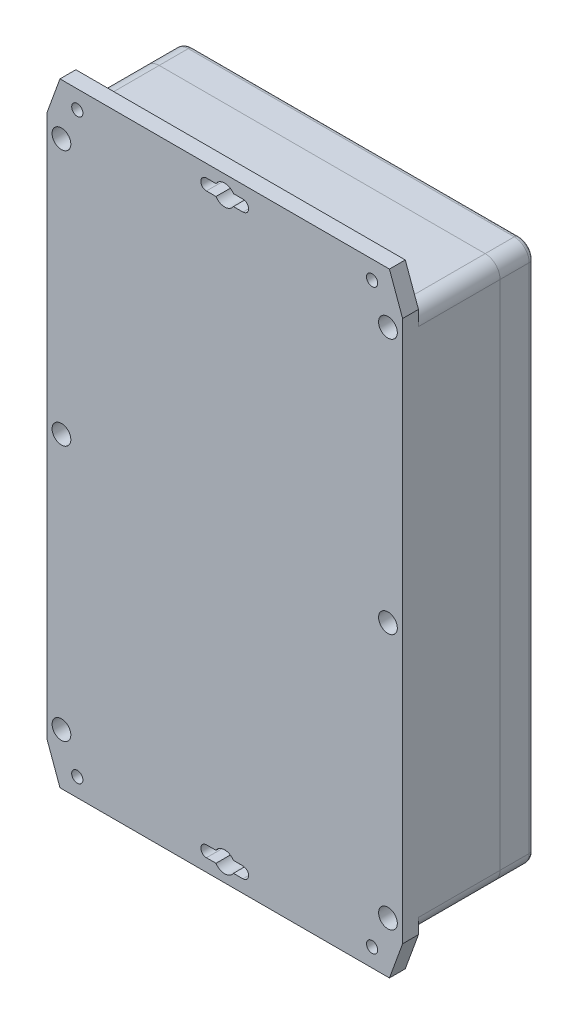
SolidWorks part; units mm, degrees
ref_plane "Front Plane" through (0, 0, 0) normal (0, 0, 1) x (1, 0, 0)
ref_plane "Top Plane" through (0, 0, 0) normal (0, 1, 0) x (1, 0, 0)
ref_plane "Right Plane" through (0, 0, 0) normal (1, 0, 0) x (0, 0, -1)
sketch "Sketch1" plane through (0, 0, 0) normal (0, 0, 1) x (1, 0, 0)
  line L0 (-73.025, -125.9967) -> (73.025, 125.9967) construction
  line L1 (-73.025, 125.9967) -> (73.025, 125.9967)
  line L2 (-73.025, 125.9967) -> (-73.025, -125.9967)
  line L3 (-73.025, -125.9967) -> (73.025, -125.9967)
  line L4 (73.025, 125.9967) -> (73.025, -125.9967)
  line L5 (0, 118.5037) -> (0, -118.5037) construction
  line L6 (-7.5057, 118.5037) -> (7.5057, 118.5037) construction
  line L7 (-7.5057, 120.8024) -> (-3.58, 120.8024)
  line L8 (-7.5057, 116.205) -> (-3.58, 116.205)
  line L9 (3.58, 120.8024) -> (7.5057, 120.8024)
  line L10 (3.58, 116.205) -> (7.5057, 116.205)
  line L11 (-73.025, 0) -> (73.025, 0) construction
  line L12 (-7.5057, -116.205) -> (-3.58, -116.205)
  line L13 (3.58, -116.205) -> (7.5057, -116.205)
  line L14 (3.58, -120.8024) -> (7.5057, -120.8024)
  line L15 (-7.5057, -120.8024) -> (-3.58, -120.8024)
  line L16 (-67.0052, 105.0036) -> (67.0052, -105.0036) construction
  line L17 (0, -114.2492) -> (0, -122.7582) construction
  line L18 (0, 114.2492) -> (0, 122.7582) construction
  line L19 (-60.5028, 118.5037) -> (60.5028, 118.5037) construction
  line L20 (-60.5028, -118.5037) -> (60.5028, -118.5037) construction
  line L21 (0, -118.5037) -> (0, 118.5037) construction
  arc A0 (3.58, 120.8024) -> (-3.58, 120.8024) centre (0, 118.5037) ccw
  arc A1 (-7.5057, 120.8024) -> (-7.5057, 116.205) centre (-7.5057, 118.5037) ccw
  arc A2 (7.5057, 116.205) -> (7.5057, 120.8024) centre (7.5057, 118.5037) ccw
  arc A3 (-3.58, 116.205) -> (3.58, 116.205) centre (0, 118.5037) ccw
  arc A4 (-3.58, -116.205) -> (3.58, -116.205) centre (0, -118.5037) cw
  arc A5 (7.5057, -116.205) -> (7.5057, -120.8024) centre (7.5057, -118.5037) cw
  arc A6 (3.58, -120.8024) -> (-3.58, -120.8024) centre (0, -118.5037) cw
  arc A7 (-7.5057, -120.8024) -> (-7.5057, -116.205) centre (-7.5057, -118.5037) cw
  circle A8 centre (67.0052, 105.0036) radius 2.2225
  circle A9 centre (67.0052, 105.0036) radius 3.8481
  circle A10 centre (67.0052, -105.0036) radius 3.8481
  circle A11 centre (67.0052, -105.0036) radius 2.2225
  circle A12 centre (-67.0052, -105.0036) radius 3.8481
  circle A13 centre (-67.0052, -105.0036) radius 2.2225
  circle A14 centre (-67.0052, 105.0036) radius 3.8481
  circle A15 centre (-67.0052, 105.0036) radius 2.2225
  circle A16 centre (60.5028, 118.5037) radius 2.2987
  circle A17 centre (-60.5028, 118.5037) radius 2.2987
  circle A18 centre (-60.5028, -118.5037) radius 2.2987
  circle A19 centre (60.5028, -118.5037) radius 2.2987
  circle A20 centre (-67.0052, 0) radius 3.8481
  circle A21 centre (-67.0052, 0) radius 2.2225
  circle A22 centre (67.0052, 0) radius 3.8481
  circle A23 centre (67.0052, 0) radius 2.2225
  dimension "D4" = 8.509
  dimension "D5" = 4.5974
  dimension "D7" = 7.6962
  dimension "D8" = 4.445
  dimension "Width" = 146.05
  dimension "Total Height" = 251.9934
  dimension "Hole Location" = 237.0074
  dimension "D6" = 15.0114
  dimension "A" = 210.0072
  dimension "B" = 134.0104
  dimension "flange holes" = 121.0056
sketch "Sketch18" plane through (0, 0, 0) normal (1, 0, 0) x (0, 0, -1)
  line L0 (0, 0) -> (53.975, 0) construction
  point P3 (40.005, 0)
  dimension "Depth" = 53.975
  dimension "Base Depth" = 40.005
sketch "Sketch2" plane through (0, 0, 0) normal (0, 0, 1) x (1, 0, 0)
  line L4 (73.025, 125.9967) -> (-73.025, 125.9967)
  line L5 (73.025, -125.9967) -> (73.025, 125.9967)
  line L6 (-73.025, -125.9967) -> (73.025, -125.9967)
  line L7 (-73.025, 125.9967) -> (-73.025, -125.9967)
  line L8 (73.025, 125.9967) -> (-73.025, 125.9967)
  line L9 (73.025, -125.9967) -> (73.025, 125.9967)
  line L10 (-73.025, -125.9967) -> (73.025, -125.9967)
  line L11 (-73.025, 125.9967) -> (-73.025, -125.9967)
  line L12 (-7.5057, -120.8024) -> (-3.58, -120.8024)
  line L13 (3.58, -120.8024) -> (7.5057, -120.8024)
  line L14 (7.5057, -116.205) -> (3.58, -116.205)
  line L15 (-3.58, -116.205) -> (-7.5057, -116.205)
  line L16 (-7.5057, -120.8024) -> (-3.58, -120.8024)
  line L17 (3.58, -120.8024) -> (7.5057, -120.8024)
  line L18 (7.5057, -116.205) -> (3.58, -116.205)
  line L19 (-3.58, -116.205) -> (-7.5057, -116.205)
  line L20 (-3.58, 120.8024) -> (-7.5057, 120.8024)
  line L21 (-7.5057, 116.205) -> (-3.58, 116.205)
  line L22 (3.58, 116.205) -> (7.5057, 116.205)
  line L23 (7.5057, 120.8024) -> (3.58, 120.8024)
  line L24 (-3.58, 120.8024) -> (-7.5057, 120.8024)
  line L25 (-7.5057, 116.205) -> (-3.58, 116.205)
  line L26 (3.58, 116.205) -> (7.5057, 116.205)
  line L27 (7.5057, 120.8024) -> (3.58, 120.8024)
  circle A0 centre (60.5028, 118.5037) radius 2.2987 construction
  circle A1 centre (-60.5028, 118.5037) radius 2.2987 construction
  circle A2 centre (-60.5028, -118.5037) radius 2.2987 construction
  circle A3 centre (60.5028, -118.5037) radius 2.2987 construction
  circle A4 centre (60.5028, 118.5037) radius 2.2987
  circle A5 centre (-60.5028, 118.5037) radius 2.2987
  circle A6 centre (-60.5028, -118.5037) radius 2.2987
  circle A7 centre (60.5028, -118.5037) radius 2.2987
  arc A8 (-7.5057, -116.205) -> (-7.5057, -120.8024) centre (-7.5057, -118.5037) ccw
  arc A9 (-3.58, -120.8024) -> (3.58, -120.8024) centre (0, -118.5037) ccw
  arc A10 (7.5057, -120.8024) -> (7.5057, -116.205) centre (7.5057, -118.5037) ccw
  arc A11 (3.58, -116.205) -> (-3.58, -116.205) centre (0, -118.5037) ccw
  arc A12 (-7.5057, -116.205) -> (-7.5057, -120.8024) centre (-7.5057, -118.5037) ccw
  arc A13 (-3.58, -120.8024) -> (3.58, -120.8024) centre (0, -118.5037) ccw
  arc A14 (7.5057, -120.8024) -> (7.5057, -116.205) centre (7.5057, -118.5037) ccw
  arc A15 (3.58, -116.205) -> (-3.58, -116.205) centre (0, -118.5037) ccw
  arc A16 (-7.5057, 120.8024) -> (-7.5057, 116.205) centre (-7.5057, 118.5037) ccw
  arc A17 (-3.58, 116.205) -> (3.58, 116.205) centre (0, 118.5037) ccw
  arc A18 (7.5057, 116.205) -> (7.5057, 120.8024) centre (7.5057, 118.5037) ccw
  arc A19 (3.58, 120.8024) -> (-3.58, 120.8024) centre (0, 118.5037) ccw
  arc A20 (-7.5057, 120.8024) -> (-7.5057, 116.205) centre (-7.5057, 118.5037) ccw
  arc A21 (-3.58, 116.205) -> (3.58, 116.205) centre (0, 118.5037) ccw
  arc A22 (7.5057, 116.205) -> (7.5057, 120.8024) centre (7.5057, 118.5037) ccw
  arc A23 (3.58, 120.8024) -> (-3.58, 120.8024) centre (0, 118.5037) ccw
  dimension "D1" = 0
  dimension "D4" = 0
  dimension "D5" = 0
extrude "Boss-Extrude1" add sketch "Sketch2" against normal blind 6.5024
sketch "Sketch3" plane through (0, 0, -6.5024) normal (0, 0, -1) x (-1, 0, 0)
  line L0 (73.025, 111.125) -> (67.6121, 125.9967)
  line L1 (-73.025, 111.125) -> (-67.6121, 125.9967)
  line L2 (73.025, -111.125) -> (67.6121, -125.9967)
  line L3 (-73.025, -111.125) -> (-67.6121, -125.9967)
  line L4 (73.025, -125.9967) -> (73.025, 125.9967)
  line L5 (73.025, 125.9967) -> (-73.025, 125.9967)
  line L6 (-73.025, 125.9967) -> (-73.025, -125.9967)
  line L7 (-73.025, -125.9967) -> (73.025, -125.9967)
  line L8 (73.025, -125.9967) -> (73.025, -111.125)
  line L9 (73.025, 125.9967) -> (67.6121, 125.9967)
  line L10 (-73.025, 125.9967) -> (-73.025, 111.125)
  line L11 (-73.025, -125.9967) -> (-67.6121, -125.9967)
  line L12 (-67.6121, 125.9967) -> (-73.025, 125.9967)
  line L13 (73.025, -125.9967) -> (-73.025, -125.9967) construction
  line L14 (67.6121, -125.9967) -> (73.025, -125.9967)
  line L15 (-73.025, -111.125) -> (-73.025, -125.9967)
  line L16 (73.025, 111.125) -> (73.025, 125.9967)
  line L19 (73.025, 111.125) -> (73.025, -111.125) construction
  dimension "D2" = 20
  dimension "D3" = 20
  dimension "Height" = 222.25
  dimension "D1" = 0
extrude "Cut-Extrude1" cut sketch "Sketch3" against normal through all
sketch "Sketch4" plane through (0, 0, -6.5024) normal (0, 0, 1) x (1, 0, 0)
  line L0 (-68.453, 106.553) -> (68.453, 106.553) construction
  line L1 (-73.025, 111.125) -> (73.025, 111.125)
  line L2 (-73.025, 111.125) -> (-73.025, -111.125)
  line L3 (-73.025, -111.125) -> (73.025, -111.125)
  line L4 (73.025, 111.125) -> (73.025, -111.125)
  line L5 (68.453, 106.553) -> (68.453, -106.553) construction
  line L6 (-68.453, -106.553) -> (68.453, -106.553) construction
  line L7 (-68.453, 106.553) -> (-68.453, -106.553) construction
  line L8 (-70.485, 108.585) -> (70.485, 108.585) construction
  line L9 (73.025, 125.9967) -> (73.025, -125.9967) construction
  line L10 (70.485, 108.585) -> (70.485, -108.585) construction
  line L11 (-70.485, -108.585) -> (70.485, -108.585) construction
  line L12 (-70.485, 108.585) -> (-70.485, -108.585) construction
  circle A0 centre (67.0052, 105.0036) radius 6.1214 construction
  circle A1 centre (-67.0052, 105.0036) radius 6.1214 construction
  circle A2 centre (-67.0052, -105.0036) radius 6.1214 construction
  circle A3 centre (67.0052, -105.0036) radius 6.1214 construction
  dimension "D3" = 12.2428
  dimension "D1" = 4.572
  dimension "D2" = 2.032
extrude "Boss-Extrude2" add sketch "Sketch4" against normal up to vertex (33.5026 mm away) up to point (0, 0, -40.005)
sketch "Sketch5" plane through (0, 0, 0) normal (0, 0, -1) x (-1, 0, 0)
  circle A0 centre (67.0052, 105.0036) radius 3.8481 construction
  circle A1 centre (-67.0052, 105.0036) radius 3.8481 construction
  circle A2 centre (-67.0052, -105.0036) radius 3.8481 construction
  circle A3 centre (67.0052, -105.0036) radius 3.8481 construction
  circle A4 centre (67.0052, 105.0036) radius 3.8481
  circle A5 centre (-67.0052, 105.0036) radius 3.8481
  circle A6 centre (-67.0052, -105.0036) radius 3.8481
  circle A7 centre (67.0052, -105.0036) radius 3.8481
  circle A8 centre (-67.0052, 0) radius 3.8481 construction
  circle A9 centre (67.0052, 0) radius 3.8481 construction
  circle A10 centre (-67.0052, 0) radius 3.8481
  circle A11 centre (67.0052, 0) radius 3.8481
extrude "Cut-Extrude2" cut sketch "Sketch5" along normal blind 24.003
sketch "Sketch6" plane through (0, 0, -24.003) normal (0, 0, 1) x (1, 0, 0)
  circle A0 centre (-67.0052, 105.0036) radius 2.2225 construction
  circle A1 centre (67.0052, 105.0036) radius 2.2225 construction
  circle A2 centre (67.0052, -105.0036) radius 2.2225 construction
  circle A3 centre (-67.0052, -105.0036) radius 2.2225 construction
  circle A4 centre (-67.0052, 105.0036) radius 2.2225
  circle A5 centre (67.0052, 105.0036) radius 2.2225
  circle A6 centre (67.0052, -105.0036) radius 2.2225
  circle A7 centre (-67.0052, -105.0036) radius 2.2225
  circle A8 centre (67.0052, 0) radius 2.2225 construction
  circle A9 centre (-67.0052, 0) radius 2.2225 construction
  circle A10 centre (67.0052, 0) radius 2.2225
  circle A11 centre (-67.0052, 0) radius 2.2225
extrude "Cut-Extrude3" cut sketch "Sketch6" against normal through all
sketch "Sketch7" plane through (0, 0, -40.005) normal (0, 0, -1) x (-1, 0, 0)
  line L0 (70.485, 108.585) -> (-70.485, 108.585) construction
  line L1 (70.485, 108.585) -> (70.485, -108.585) construction
  line L2 (-70.485, 108.585) -> (-70.485, -108.585) construction
  line L4 (46.6471, 108.585) -> (-46.6471, 108.585)
  line L5 (70.485, 95.4024) -> (70.485, -95.4024)
  line L6 (-70.485, 95.4024) -> (-70.485, -95.4024)
  line L8 (-51.4985, 103.7336) -> (-51.4985, 98.8822) construction
  line L9 (-67.0052, 98.8822) -> (-56.3499, 98.8822)
  line L12 (46.6471, -108.585) -> (-46.6471, -108.585)
  line L13 (0, 0) -> (0, 108.585) construction
  line L14 (67.0052, 98.8822) -> (56.3499, 98.8822)
  line L15 (0, 0) -> (-70.485, 0) construction
  line L16 (67.0052, -98.8822) -> (56.3499, -98.8822)
  line L17 (-67.0052, -98.8822) -> (-56.3499, -98.8822)
  circle A0 centre (-67.0052, 105.0036) radius 6.1214 construction
  arc A1 (51.4985, -103.7336) -> (46.6471, -108.585) centre (46.6471, -103.7336) cw
  circle A2 centre (67.0052, -105.0036) radius 6.1214 construction
  circle A4 centre (-67.0052, 105.0036) radius 6.1214 construction
  circle A6 centre (67.0052, -105.0036) radius 6.1214 construction
  arc A14 (-67.0052, 98.8822) -> (-70.485, 95.4024) centre (-67.0052, 95.4024) ccw
  arc A22 (-51.4985, 103.7336) -> (-46.6471, 108.585) centre (-46.6471, 103.7336) cw
  arc A24 (67.0052, 98.8822) -> (70.485, 95.4024) centre (67.0052, 95.4024) cw
  arc A25 (-56.3499, 98.8822) -> (-51.4985, 103.7336) centre (-56.3499, 103.7336) ccw
  circle A26 centre (-67.0052, 105.0036) radius 2.2225 construction
  circle A27 centre (67.0052, 105.0036) radius 6.1214 construction
  arc A28 (56.3499, 98.8822) -> (51.4985, 103.7336) centre (56.3499, 103.7336) cw
  arc A29 (51.4985, 103.7336) -> (46.6471, 108.585) centre (46.6471, 103.7336) ccw
  arc A30 (56.3499, -98.8822) -> (51.4985, -103.7336) centre (56.3499, -103.7336) ccw
  arc A31 (-51.4985, -103.7336) -> (-46.6471, -108.585) centre (-46.6471, -103.7336) ccw
  arc A32 (-56.3499, -98.8822) -> (-51.4985, -103.7336) centre (-56.3499, -103.7336) cw
  arc A33 (67.0052, -98.8822) -> (70.485, -95.4024) centre (67.0052, -95.4024) ccw
  arc A34 (-67.0052, -98.8822) -> (-70.485, -95.4024) centre (-67.0052, -95.4024) cw
  dimension "D1" = 102.997
sketch "Sketch8" plane through (0, 0, -40.005) normal (0, 0, -1) x (-1, 0, 0)
  line L0 (-67.0052, -6.1214) -> (-70.485, -6.1214)
  line L1 (-67.0052, 6.1214) -> (-70.485, 6.1214)
  line L2 (67.0052, 6.1214) -> (70.485, 6.1214)
  line L3 (67.0052, -6.1214) -> (70.485, -6.1214)
  line L4 (-70.485, -6.1214) -> (-70.485, -95.4024)
  line L5 (70.485, 6.1214) -> (70.485, 95.4024)
  line L8 (46.6471, 108.585) -> (-46.6471, 108.585)
  line L9 (-56.3499, 98.8822) -> (-67.0052, 98.8822)
  line L10 (-70.485, 95.4024) -> (-70.485, -95.4024)
  line L11 (-67.0052, -98.8822) -> (-56.3499, -98.8822)
  line L12 (-46.6471, -108.585) -> (46.6471, -108.585)
  line L13 (56.3499, -98.8822) -> (67.0052, -98.8822)
  line L14 (70.485, -95.4024) -> (70.485, 95.4024)
  line L15 (67.0052, 98.8822) -> (56.3499, 98.8822)
  line L16 (46.6471, 108.585) -> (-46.6471, 108.585)
  line L17 (-56.3499, 98.8822) -> (-67.0052, 98.8822)
  line L18 (-70.485, 95.4024) -> (-70.485, 6.1214)
  line L19 (-67.0052, -98.8822) -> (-56.3499, -98.8822)
  line L20 (-46.6471, -108.585) -> (46.6471, -108.585)
  line L21 (56.3499, -98.8822) -> (67.0052, -98.8822)
  line L22 (70.485, -95.4024) -> (70.485, -6.1214)
  line L23 (67.0052, 98.8822) -> (56.3499, 98.8822)
  arc A0 (-67.0052, -6.1214) -> (-67.0052, 6.1214) centre (-67.0052, 0) ccw
  arc A1 (67.0052, 6.1214) -> (67.0052, -6.1214) centre (67.0052, 0) ccw
  circle A4 centre (-67.0052, 105.0036) radius 6.1214 construction
  arc A13 (-46.6471, 108.585) -> (-51.4985, 103.7336) centre (-46.6471, 103.7336) ccw
  arc A14 (-56.3499, 98.8822) -> (-51.4985, 103.7336) centre (-56.3499, 103.7336) ccw
  arc A15 (-67.0052, 98.8822) -> (-70.485, 95.4024) centre (-67.0052, 95.4024) ccw
  arc A16 (-70.485, -95.4024) -> (-67.0052, -98.8822) centre (-67.0052, -95.4024) ccw
  arc A17 (-51.4985, -103.7336) -> (-56.3499, -98.8822) centre (-56.3499, -103.7336) ccw
  arc A18 (-51.4985, -103.7336) -> (-46.6471, -108.585) centre (-46.6471, -103.7336) ccw
  arc A19 (46.6471, -108.585) -> (51.4985, -103.7336) centre (46.6471, -103.7336) ccw
  arc A20 (56.3499, -98.8822) -> (51.4985, -103.7336) centre (56.3499, -103.7336) ccw
  arc A21 (67.0052, -98.8822) -> (70.485, -95.4024) centre (67.0052, -95.4024) ccw
  arc A22 (70.485, 95.4024) -> (67.0052, 98.8822) centre (67.0052, 95.4024) ccw
  arc A23 (51.4985, 103.7336) -> (56.3499, 98.8822) centre (56.3499, 103.7336) ccw
  arc A24 (51.4985, 103.7336) -> (46.6471, 108.585) centre (46.6471, 103.7336) ccw
  arc A25 (-46.6471, 108.585) -> (-51.4985, 103.7336) centre (-46.6471, 103.7336) ccw
  arc A26 (-56.3499, 98.8822) -> (-51.4985, 103.7336) centre (-56.3499, 103.7336) ccw
  arc A27 (-67.0052, 98.8822) -> (-70.485, 95.4024) centre (-67.0052, 95.4024) ccw
  arc A28 (-70.485, -95.4024) -> (-67.0052, -98.8822) centre (-67.0052, -95.4024) ccw
  arc A29 (-51.4985, -103.7336) -> (-56.3499, -98.8822) centre (-56.3499, -103.7336) ccw
  arc A30 (-51.4985, -103.7336) -> (-46.6471, -108.585) centre (-46.6471, -103.7336) ccw
  arc A31 (46.6471, -108.585) -> (51.4985, -103.7336) centre (46.6471, -103.7336) ccw
  arc A32 (56.3499, -98.8822) -> (51.4985, -103.7336) centre (56.3499, -103.7336) ccw
  arc A33 (67.0052, -98.8822) -> (70.485, -95.4024) centre (67.0052, -95.4024) ccw
  arc A34 (70.485, 95.4024) -> (67.0052, 98.8822) centre (67.0052, 95.4024) ccw
  arc A35 (51.4985, 103.7336) -> (56.3499, 98.8822) centre (56.3499, 103.7336) ccw
  arc A36 (51.4985, 103.7336) -> (46.6471, 108.585) centre (46.6471, 103.7336) ccw
  point P2 (-19.1135, 50.2285)
  point P3 (-19.1135, 56.896)
  point P4 (22.9997, -25.9969)
  point P8 (-25.781, 50.2285)
  point P11 (-26.035, 21.1097)
  point P13 (26.035, -21.1097)
  point P14 (-27.8765, 48.133)
  point P18 (-41.91, -42.9387)
  point P19 (-39.0017, 48.133)
  point P29 (-19.1135, 50.2285)
  point P30 (-19.1135, 56.896)
  point P33 (41.91, 42.9387)
  point P34 (-25.781, 50.2285)
  point P37 (-27.8765, 48.133)
  point P39 (-39.0017, 48.133)
  point P52 (31.0388, -25.9969)
  point P57 (-24.003, -17.2085)
  point P58 (-24.003, 18.2767)
  point P59 (-22.9997, 25.9969)
  point P60 (-15.2146, 25.9969)
  point P61 (-19.2786, 25.9969)
  point P62 (-19.2786, 16.0147)
  point P63 (-22.9997, 25.9969)
  point P64 (-19.2786, 25.9969)
  point P65 (-14.9606, 25.9969)
  point P67 (-22.9997, 12.2936)
  point P68 (-19.2786, 15.8369)
  point P69 (-22.9997, 7.2263)
  point P70 (-28.067, 7.2263)
  point P75 (15.2146, -25.9969)
  point P97 (24.003, 17.2085)
  point P98 (24.003, -18.2767)
  point P99 (22.9997, -25.9969)
  point P100 (22.9997, -7.2263)
  point P101 (22.9997, -12.2936)
  point P102 (28.067, -7.2263)
  point P104 (19.2786, -16.0147)
  point P105 (19.2786, -25.9969)
  dimension "D1" = 0
extrude "Cut-Extrude4" cut sketch "Sketch8" against normal offset from surface (37.0078 mm away) 2.9972 up to face at (63.1571, 0, 0)
sketch "Sketch9" plane through (0, 0, 0) normal (0, 0, -1) x (-1, 0, 0)
  line L1 (-19.4945, 82.9945) -> (19.4945, 82.9945) construction
  line L2 (0, 82.9945) -> (0, 0) construction
  line L3 (0, 82.9945) -> (0, 90.7542) construction
  line L4 (-57.7469, 90.7542) -> (57.7469, 90.7542) construction
  line L5 (0, 0) -> (-36.6733, 0) construction
  line L6 (-57.7469, -90.7542) -> (57.7469, -90.7542) construction
  line L7 (-19.4945, -82.9945) -> (19.4945, -82.9945) construction
  line L8 (0, -82.9945) -> (0, -90.7542) construction
  line L9 (0, -82.9945) -> (0, 0) construction
  circle A0 centre (-57.7469, 90.7542) radius 3.0099
  circle A1 centre (-57.7469, 90.7542) radius 1.2446
  circle A2 centre (57.7469, 90.7542) radius 3.0099
  circle A3 centre (57.7469, 90.7542) radius 1.2446
  circle A4 centre (-19.4945, 82.9945) radius 3.0099
  circle A5 centre (-19.4945, 82.9945) radius 1.2446
  circle A6 centre (19.4945, 82.9945) radius 3.0099
  circle A7 centre (19.4945, 82.9945) radius 1.2446
  circle A8 centre (57.7469, -90.7542) radius 1.2446
  circle A9 centre (57.7469, -90.7542) radius 3.0099
  circle A10 centre (19.4945, -82.9945) radius 1.2446
  circle A11 centre (-19.4945, -82.9945) radius 1.2446
  circle A12 centre (-19.4945, -82.9945) radius 3.0099
  circle A13 centre (-57.7469, -90.7542) radius 1.2446
  circle A14 centre (-57.7469, -90.7542) radius 3.0099
  circle A15 centre (19.4945, -82.9945) radius 3.0099
  dimension "D2" = 2.4892
  dimension "D3" = 6.0198
  dimension "D1" = 2.4892
  dimension "D4" = 6.0198
  dimension "D5" = 2.4892
  dimension "D6" = 6.0198
  dimension "D9" = 165.989
  dimension "D10" = 181.5084
  dimension "D7" = 38.989
  dimension "D8" = 115.4938
extrude "Boss-Extrude3" add sketch "Sketch9" along normal blind 7.493
fillet "Fillet2" radius 6.1214 4 edges at (73.025, 111.125, -23.2537) (73.025, -111.125, -23.2537) (-73.025, -111.125, -23.2537) (-73.025, 111.125, -23.2537) tangent propagation no
sketch "Sketch11" plane through (0, 0, -40.005) normal (0, 0, -1) x (-1, 0, 0)
  line L4 (-73.025, 105.0036) -> (-73.025, -105.0036)
  line L5 (66.9036, 111.125) -> (-66.9036, 111.125)
  line L6 (73.025, -105.0036) -> (73.025, 105.0036)
  line L7 (-66.9036, -111.125) -> (66.9036, -111.125)
  line L8 (-73.025, 105.0036) -> (-73.025, -105.0036)
  line L9 (66.9036, 111.125) -> (-66.9036, 111.125)
  line L10 (73.025, -105.0036) -> (73.025, 105.0036)
  line L11 (-66.9036, -111.125) -> (66.9036, -111.125)
  arc A4 (-66.9036, 111.125) -> (-73.025, 105.0036) centre (-66.9036, 105.0036) ccw
  arc A5 (73.025, 105.0036) -> (66.9036, 111.125) centre (66.9036, 105.0036) ccw
  arc A6 (66.9036, -111.125) -> (73.025, -105.0036) centre (66.9036, -105.0036) ccw
  arc A7 (-73.025, -105.0036) -> (-66.9036, -111.125) centre (-66.9036, -105.0036) ccw
  arc A8 (-66.9036, 111.125) -> (-73.025, 105.0036) centre (-66.9036, 105.0036) ccw
  arc A9 (73.025, 105.0036) -> (66.9036, 111.125) centre (66.9036, 105.0036) ccw
  arc A10 (66.9036, -111.125) -> (73.025, -105.0036) centre (66.9036, -105.0036) ccw
  arc A11 (-73.025, -105.0036) -> (-66.9036, -111.125) centre (-66.9036, -105.0036) ccw
  dimension "D1" = 0
extrude "Boss-Extrude4" add sketch "Sketch11" along normal up to vertex (13.97 mm away) separate body up to point (0, 0, -53.975)
sketch "Sketch12" plane through (0, 0, -53.975) normal (0, 0, -1) x (-1, 0, 0)
  circle A0 centre (-67.0052, 105.0036) radius 3.8481 construction
  circle A1 centre (67.0052, 105.0036) radius 3.8481 construction
  circle A2 centre (67.0052, -105.0036) radius 3.8481 construction
  circle A3 centre (-67.0052, -105.0036) radius 3.8481 construction
  circle A4 centre (-67.0052, 105.0036) radius 3.8481
  circle A5 centre (67.0052, 105.0036) radius 3.8481
  circle A6 centre (67.0052, -105.0036) radius 3.8481
  circle A7 centre (-67.0052, -105.0036) radius 3.8481
  circle A8 centre (-67.0052, 0) radius 3.8481 construction
  circle A9 centre (67.0052, 0) radius 3.8481 construction
  circle A10 centre (-67.0052, 0) radius 3.8481
  circle A11 centre (67.0052, 0) radius 3.8481
extrude "Cut-Extrude5" cut sketch "Sketch12" against normal blind 3.2004
shell "Shell1" thickness 2.9972 removed face at (0, 0, -40.005)
fillet "Fillet3" radius 2.032 8 edges at (-71.2321, 109.3321, -53.975) (0, 111.125, -53.975) (71.2321, 109.3321, -53.975) (73.025, 0, -53.975) (71.2321, -109.3321, -53.975) (0, -111.125, -53.975) (-71.2321, -109.3321, -53.975) (-73.025, 0, -53.975)
sketch "Sketch13" plane through (0, 0, -50.7746) normal (0, 0, -1) x (-1, 0, 0)
  circle A0 centre (-67.0052, 0) radius 3.5941
  circle A1 centre (67.0052, 105.0036) radius 3.5941
  circle A2 centre (-67.0052, 105.0036) radius 3.5941
  circle A3 centre (-67.0052, 105.0036) radius 3.5941
  circle A4 centre (67.0052, -105.0036) radius 3.5941
  circle A5 centre (-67.0052, -105.0036) radius 3.5941
  circle A6 centre (67.0052, 0) radius 3.5941
  dimension "D1" = 0.254
extrude "Boss-Extrude6" add sketch "Sketch13" along normal blind 2.286 separate body
sketch "Sketch14" plane through (0, 0, -50.7746) normal (0, 0, 1) x (1, 0, 0)
  circle A0 centre (-67.0052, 105.0036) radius 2.2225 construction
  circle A1 centre (-67.0052, 105.0036) radius 2.2225
  circle A2 centre (-67.0052, -105.0036) radius 2.2225 construction
  circle A3 centre (67.0052, -105.0036) radius 2.2225 construction
  circle A4 centre (-67.0052, -105.0036) radius 2.2225
  circle A5 centre (67.0052, -105.0036) radius 2.2225
  circle A6 centre (67.0052, 105.0036) radius 2.2225 construction
  circle A7 centre (67.0052, 105.0036) radius 2.2225
  circle A8 centre (67.0052, 0) radius 2.2225 construction
  circle A9 centre (67.0052, 0) radius 2.2225
  circle A10 centre (-67.0052, 0) radius 2.2225 construction
  circle A11 centre (-67.0052, 0) radius 2.2225
extrude "Boss-Extrude7" add sketch "Sketch14" along normal offset from surface (29.8196 mm away) 3.048 up to face at (-64.7827, 105.0036, -24.003) offset beyond the face yes
fillet "Fillet4" radius 1.27 6 edges at (-70.5993, -105.0036, -53.0606) (63.4111, -105.0036, -53.0606) (-70.5993, 105.0036, -53.0606) (63.4111, 105.0036, -53.0606) (-70.5993, 0, -53.0606) (63.4111, 0, -53.0606)
sketch "Sketch15" plane through (0, 0, -53.0606) normal (0, 0, -1) x (-1, 0, 0)
  line L0 (-67.0052, 111.125) -> (-67.0052, -111.125)
  line L1 (-66.9036, -111.125) -> (66.9036, -111.125) construction
  line L2 (66.9036, 111.125) -> (-66.9036, 111.125) construction
  circle A0 centre (-67.0052, 105.0036) radius 2.3241 construction
  circle A1 centre (-67.0052, 105.0036) radius 2.3241 construction
extrude "Cut-Extrude-Thin1" cut sketch "Sketch15" against normal blind 1.524 thin thin type mid plane wall 1.524
mirror "Mirror1" about plane through (0, 0, 0) normal (1, 0, 0) of "Cut-Extrude-Thin1"
sketch "Sketch16" plane through (0, 0, -40.005) normal (0, 0, -1) x (-1, 0, 0)
  line L8 (46.6471, 108.585) -> (-46.6471, 108.585)
  line L9 (-56.3499, 98.8822) -> (-67.0052, 98.8822)
  line L10 (-70.485, 95.4024) -> (-70.485, -95.4024)
  line L11 (-67.0052, -98.8822) -> (-56.3499, -98.8822)
  line L12 (-46.6471, -108.585) -> (46.6471, -108.585)
  line L13 (56.3499, -98.8822) -> (67.0052, -98.8822)
  line L14 (70.485, -95.4024) -> (70.485, 95.4024)
  line L15 (67.0052, 98.8822) -> (56.3499, 98.8822)
  line L16 (46.6471, 108.585) -> (-46.6471, 108.585)
  line L17 (-56.3499, 98.8822) -> (-67.0052, 98.8822)
  line L18 (-70.485, 95.4024) -> (-70.485, -95.4024)
  line L19 (-67.0052, -98.8822) -> (-56.3499, -98.8822)
  line L20 (-46.6471, -108.585) -> (46.6471, -108.585)
  line L21 (56.3499, -98.8822) -> (67.0052, -98.8822)
  line L22 (70.485, -95.4024) -> (70.485, 95.4024)
  line L23 (67.0052, 98.8822) -> (56.3499, 98.8822)
  arc A12 (-46.6471, 108.585) -> (-51.4985, 103.7336) centre (-46.6471, 103.7336) ccw
  arc A13 (-56.3499, 98.8822) -> (-51.4985, 103.7336) centre (-56.3499, 103.7336) ccw
  arc A14 (-67.0052, 98.8822) -> (-70.485, 95.4024) centre (-67.0052, 95.4024) ccw
  arc A15 (-70.485, -95.4024) -> (-67.0052, -98.8822) centre (-67.0052, -95.4024) ccw
  arc A16 (-51.4985, -103.7336) -> (-56.3499, -98.8822) centre (-56.3499, -103.7336) ccw
  arc A17 (-51.4985, -103.7336) -> (-46.6471, -108.585) centre (-46.6471, -103.7336) ccw
  arc A18 (46.6471, -108.585) -> (51.4985, -103.7336) centre (46.6471, -103.7336) ccw
  arc A19 (56.3499, -98.8822) -> (51.4985, -103.7336) centre (56.3499, -103.7336) ccw
  arc A20 (67.0052, -98.8822) -> (70.485, -95.4024) centre (67.0052, -95.4024) ccw
  arc A21 (70.485, 95.4024) -> (67.0052, 98.8822) centre (67.0052, 95.4024) ccw
  arc A22 (51.4985, 103.7336) -> (56.3499, 98.8822) centre (56.3499, 103.7336) ccw
  arc A23 (51.4985, 103.7336) -> (46.6471, 108.585) centre (46.6471, 103.7336) ccw
  arc A24 (-46.6471, 108.585) -> (-51.4985, 103.7336) centre (-46.6471, 103.7336) ccw
  arc A25 (-56.3499, 98.8822) -> (-51.4985, 103.7336) centre (-56.3499, 103.7336) ccw
  arc A26 (-67.0052, 98.8822) -> (-70.485, 95.4024) centre (-67.0052, 95.4024) ccw
  arc A27 (-70.485, -95.4024) -> (-67.0052, -98.8822) centre (-67.0052, -95.4024) ccw
  arc A28 (-51.4985, -103.7336) -> (-56.3499, -98.8822) centre (-56.3499, -103.7336) ccw
  arc A29 (-51.4985, -103.7336) -> (-46.6471, -108.585) centre (-46.6471, -103.7336) ccw
  arc A30 (46.6471, -108.585) -> (51.4985, -103.7336) centre (46.6471, -103.7336) ccw
  arc A31 (56.3499, -98.8822) -> (51.4985, -103.7336) centre (56.3499, -103.7336) ccw
  arc A32 (67.0052, -98.8822) -> (70.485, -95.4024) centre (67.0052, -95.4024) ccw
  arc A33 (70.485, 95.4024) -> (67.0052, 98.8822) centre (67.0052, 95.4024) ccw
  arc A34 (51.4985, 103.7336) -> (56.3499, 98.8822) centre (56.3499, 103.7336) ccw
  arc A35 (51.4985, 103.7336) -> (46.6471, 108.585) centre (46.6471, 103.7336) ccw
  dimension "D1" = 0
ref_plane "Plane1" through (0, 95.4024, 0) normal (0, 1, 0) x (-1, 0, 0)
sketch "Sketch17" plane through (0, 95.4024, 0) normal (0, 1, 0) x (-1, 0, 0)
  line L0 (-71.755, -40.005) -> (-70.485, -40.005)
  arc A0 (-71.755, -40.005) -> (-70.485, -40.005) centre (-71.12, -40.005) ccw
  dimension "D1" = 1.27
sweep "Sweep1" add profiles "Sketch17" path "Sketch16"
hole_wizard "Ø19.5 (19.5) Diameter Hole1" positions "Sketch19" profile "Sketch21" hole size "Ø19.5" standard "ISO"
sketch "Sketch19" plane through (0, -111.125, 0) normal (0, -1, 0) x (-1, 0, 0)
  line L0 (-66.9036, 23.2537) -> (66.9036, 23.2537)
  line L1 (-66.9036, 40.005) -> (-66.9036, 6.5024) construction
  line L2 (66.9036, 6.5024) -> (66.9036, 40.005) construction
  line L4 (0, 23.2537) -> (0, 30.6123)
  point P14 (-25.4, 23.2537)
  point P17 (0, 0)
  point P18 (25.4, 23.2537)
  dimension "D1" = 25.4
sketch "Sketch21" plane through (25.4, -111.125, -23.2537) normal (1, 0, 0) x (0, 0, -1)
  line L0 (0, 0) -> (0, 31.2584)
  line L1 (0, 31.2584) -> (9.75, 25.4)
  line L2 (9.75, 25.4) -> (9.75, 0)
  line L5 (9.75, 0) -> (0, 0)
  line L10 (0, 31.2584) -> (-9.75, 25.4) construction
  line L11 (0, -6.35) -> (0, 107.95) construction
  dimension "Hole Dia." = 19.5
  dimension "Hole Depth" = 25.4
  dimension "Drill Angle" = 118
equation "\"D1@Fillet2\" = \"D3@Sketch4\"/2"
equation "\"D1@Cut-Extrude2\" = \"Base Depth@Sketch18\"*.6"
